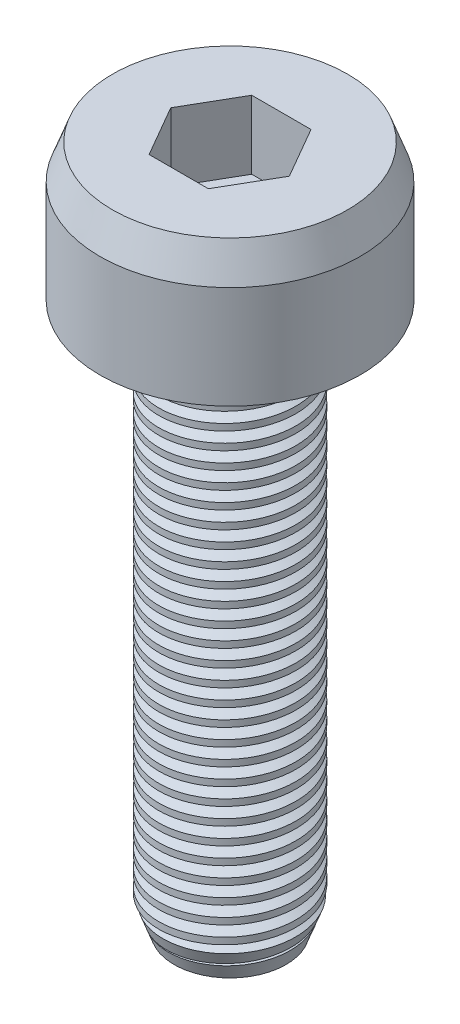
SolidWorks part; units mm, degrees
ref_plane "Front Plane" through (0, 0, 0) normal (0, 0, 1) x (1, 0, 0)
ref_plane "Top Plane" through (0, 0, 0) normal (0, 1, 0) x (1, 0, 0)
ref_plane "Right Plane" through (0, 0, 0) normal (1, 0, 0) x (0, 0, -1)
sketch "Sketch3" plane through (0, 0, 0) normal (0, 1, 0) x (1, 0, 0)
  circle A0 centre (0, 0) radius 1.9
  dimension "D1" = 3.8
extrude "Boss-Extrude3" add sketch "Sketch3" along normal blind 1.5
sketch "Sketch4" plane through (0, 1.5, 0) normal (0, 1, 0) x (1, 0, 0)
  circle A0 centre (0, 0) radius 1.9
  circle A1 centre (0, 0) radius 1.9 construction
  dimension "D1" = 3.8
extrude "Boss-Extrude5" add sketch "Sketch4" along normal blind 0.5 draft 20
sketch "Sketch6" plane through (0, 2, 0) normal (0, 1, 0) x (1, 0, 0)
  line L1 (0.866, 0) -> (0.433, 0.75)
  line L2 (0.433, 0.75) -> (-0.433, 0.75)
  line L3 (-0.433, 0.75) -> (-0.866, 0)
  line L4 (-0.866, 0) -> (-0.433, -0.75)
  line L5 (-0.433, -0.75) -> (0.433, -0.75)
  line L6 (0.433, -0.75) -> (0.866, 0)
  circle A0 centre (0, 0) radius 0.75 construction
  circle A1 centre (0, 0) radius 1.718 construction
  dimension "D1" = 1.5
extrude "Cut-Extrude1" cut sketch "Sketch6" against normal blind 1
sketch "Sketch7" plane through (0, 0, 0) normal (0, -1, 0) x (1, 0, 0)
  circle A0 centre (0, 0) radius 1
  circle A1 centre (0, 0) radius 1.9 construction
  dimension "D1" = 2
extrude "Boss-Extrude8" add sketch "Sketch7" along normal blind 7.5 contours A0
sketch "Sketch11" plane through (0, -7.5, 0) normal (0, -1, 0) x (1, 0, 0)
  circle A0 centre (0, 0) radius 1
  circle A1 centre (0, 0) radius 1 construction
  dimension "D1" = 2
extrude "Boss-Extrude9" add sketch "Sketch11" along normal blind 0.5 draft 20
sketch "Sketch12" plane through (0, -8, 0) normal (0, -1, 0) x (1, 0, 0)
  circle A0 centre (0, 0) radius 1
  circle A1 centre (0, 0) radius 0.818 construction
  dimension "D1" = 2
curve "Helix/Spiral2" pitch 0.25 height 8 turns 32
sketch "Sketch13" plane through (0, 0, 0) normal (0, 0, 1) x (1, 0, 0)
  line L1 (0.8667, -7.9956) -> (1.0572, -8.1056)
  line L2 (1.0572, -8.1056) -> (1.0572, -7.8856)
  line L3 (1.0572, -7.8856) -> (0.8667, -7.9956)
  circle A0 centre (0.9937, -7.9956) radius 0.0635 construction
  spline S0 degree 3 poles (1, -8) (1, -7.9948) (0.9479, -7.9844) (0.7255, -7.9688) (0.3926, -7.9531) (0, -7.9375) (-0.3926, -7.9219) (-0.7255, -7.9063) (-0.9479, -7.8906) (-1.026, -7.875) (-0.9479, -7.8594) (-0.7255, -7.8438) (-0.3926, -7.8281) (0, -7.8125) (0.3926, -7.7969) (0.7255, -7.7813) (0.9479, -7.7656) (1.026, -7.75) (0.9479, -7.7344) (0.7255, -7.7188) (0.3926, -7.7031) (0, -7.6875) (-0.3926, -7.6719) (-0.7255, -7.6562) (-0.9479, -7.6406) (-1.026, -7.625) (-0.9479, -7.6094) (-0.7255, -7.5937) (-0.3926, -7.5781) (0, -7.5625) (0.3926, -7.5469) (0.7255, -7.5312) (0.9479, -7.5156) (1.026, -7.5) (0.9479, -7.4844) (0.7255, -7.4687) (0.3926, -7.4531) (0, -7.4375) (-0.3926, -7.4219) (-0.7255, -7.4062) (-0.9479, -7.3906) (-1.026, -7.375) (-0.9479, -7.3594) (-0.7255, -7.3438) (-0.3926, -7.3281) (0, -7.3125) (0.3926, -7.2969) (0.7255, -7.2812) (0.9479, -7.2656) (1.026, -7.25) (0.9479, -7.2344) (0.7255, -7.2188) (0.3926, -7.2031) (0, -7.1875) (-0.3926, -7.1719) (-0.7255, -7.1563) (-0.9479, -7.1406) (-1.026, -7.125) (-0.9479, -7.1094) (-0.7255, -7.0937) (-0.3926, -7.0781) (0, -7.0625) (0.3926, -7.0469) (0.7255, -7.0312) (0.9479, -7.0156) (1.026, -7) (0.9479, -6.9844) (0.7255, -6.9687) (0.3926, -6.9531) (0, -6.9375) (-0.3926, -6.9219) (-0.7255, -6.9062) (-0.9479, -6.8906) (-1.026, -6.875) (-0.9479, -6.8594) (-0.7255, -6.8437) (-0.3926, -6.8281) (0, -6.8125) (0.3926, -6.7969) (0.7255, -6.7812) (0.9479, -6.7656) (1.026, -6.75) (0.9479, -6.7344) (0.7255, -6.7187) (0.3926, -6.7031) (0, -6.6875) (-0.3926, -6.6719) (-0.7255, -6.6562) (-0.9479, -6.6406) (-1.026, -6.625) (-0.9479, -6.6094) (-0.7255, -6.5937) (-0.3926, -6.5781) (0, -6.5625) (0.3926, -6.5469) (0.7255, -6.5312) (0.9479, -6.5156) (1.026, -6.5) (0.9479, -6.4844) (0.7255, -6.4687) (0.3926, -6.4531) (0, -6.4375) (-0.3926, -6.4219) (-0.7255, -6.4063) (-0.9479, -6.3906) (-1.026, -6.375) (-0.9479, -6.3594) (-0.7255, -6.3437) (-0.3926, -6.3281) (0, -6.3125) (0.3926, -6.2969) (0.7255, -6.2812) (0.9479, -6.2656) (1.026, -6.25) (0.9479, -6.2344) (0.7255, -6.2187) (0.3926, -6.2031) (0, -6.1875) (-0.3926, -6.1719) (-0.7255, -6.1562) (-0.9479, -6.1406) (-1.026, -6.125) (-0.9479, -6.1094) (-0.7255, -6.0937) (-0.3926, -6.0781) (0, -6.0625) (0.3926, -6.0469) (0.7255, -6.0312) (0.9479, -6.0156) (1.026, -6) (0.9479, -5.9844) (0.7255, -5.9687) (0.3926, -5.9531) (0, -5.9375) (-0.3926, -5.9219) (-0.7255, -5.9062) (-0.9479, -5.8906) (-1.026, -5.875) (-0.9479, -5.8594) (-0.7255, -5.8437) (-0.3926, -5.8281) (0, -5.8125) (0.3926, -5.7969) (0.7255, -5.7812) (0.9479, -5.7656) (1.026, -5.75) (0.9479, -5.7344) (0.7255, -5.7187) (0.3926, -5.7031) (0, -5.6875) (-0.3926, -5.6719) (-0.7255, -5.6562) (-0.9479, -5.6406) (-1.026, -5.625) (-0.9479, -5.6094) (-0.7255, -5.5937) (-0.3926, -5.5781) (0, -5.5625) (0.3926, -5.5469) (0.7255, -5.5312) (0.9479, -5.5156) (1.026, -5.5) (0.9479, -5.4844) (0.7255, -5.4687) (0.3926, -5.4531) (0, -5.4375) (-0.3926, -5.4219) (-0.7255, -5.4062) (-0.9479, -5.3906) (-1.026, -5.375) (-0.9479, -5.3594) (-0.7255, -5.3437) (-0.3926, -5.3281) (0, -5.3125) (0.3926, -5.2969) (0.7255, -5.2812) (0.9479, -5.2656) (1.026, -5.25) (0.9479, -5.2344) (0.7255, -5.2187) (0.3926, -5.2031) (0, -5.1875) (-0.3926, -5.1719) (-0.7255, -5.1562) (-0.9479, -5.1406) (-1.026, -5.125) (-0.9479, -5.1094) (-0.7255, -5.0937) (-0.3926, -5.0781) (0, -5.0625) (0.3926, -5.0469) (0.7255, -5.0312) (0.9479, -5.0156) (1.026, -5) (0.9479, -4.9844) (0.7255, -4.9687) (0.3926, -4.9531) (0, -4.9375) (-0.3926, -4.9219) (-0.7255, -4.9062) (-0.9479, -4.8906) (-1.026, -4.875) (-0.9479, -4.8594) (-0.7255, -4.8437) (-0.3926, -4.8281) (0, -4.8125) (0.3926, -4.7969) (0.7255, -4.7812) (0.9479, -4.7656) (1.026, -4.75) (0.9479, -4.7344) (0.7255, -4.7187) (0.3926, -4.7031) (0, -4.6875) (-0.3926, -4.6719) (-0.7255, -4.6562) (-0.9479, -4.6406) (-1.026, -4.625) (-0.9479, -4.6094) (-0.7255, -4.5937) (-0.3926, -4.5781) (0, -4.5625) (0.3926, -4.5469) (0.7255, -4.5312) (0.9479, -4.5156) (1.026, -4.5) (0.9479, -4.4844) (0.7255, -4.4687) (0.3926, -4.4531) (0, -4.4375) (-0.3926, -4.4219) (-0.7255, -4.4062) (-0.9479, -4.3906) (-1.026, -4.375) (-0.9479, -4.3594) (-0.7255, -4.3437) (-0.3926, -4.3281) (0, -4.3125) (0.3926, -4.2969) (0.7255, -4.2812) (0.9479, -4.2656) (1.026, -4.25) (0.9479, -4.2344) (0.7255, -4.2187) (0.3926, -4.2031) (0, -4.1875) (-0.3926, -4.1719) (-0.7255, -4.1562) (-0.9479, -4.1406) (-1.026, -4.125) (-0.9479, -4.1094) (-0.7255, -4.0937) (-0.3926, -4.0781) (0, -4.0625) (0.3926, -4.0469) (0.7255, -4.0312) (0.9479, -4.0156) (1.026, -4) (0.9479, -3.9844) (0.7255, -3.9687) (0.3926, -3.9531) (0, -3.9375) (-0.3926, -3.9219) (-0.7255, -3.9062) (-0.9479, -3.8906) (-1.026, -3.875) (-0.9479, -3.8594) (-0.7255, -3.8437) (-0.3926, -3.8281) (0, -3.8125) (0.3926, -3.7969) (0.7255, -3.7812) (0.9479, -3.7656) (1.026, -3.75) (0.9479, -3.7344) (0.7255, -3.7187) (0.3926, -3.7031) (0, -3.6875) (-0.3926, -3.6719) (-0.7255, -3.6562) (-0.9479, -3.6406) (-1.026, -3.625) (-0.9479, -3.6094) (-0.7255, -3.5937) (-0.3926, -3.5781) (0, -3.5625) (0.3926, -3.5469) (0.7255, -3.5312) (0.9479, -3.5156) (1.026, -3.5) (0.9479, -3.4844) (0.7255, -3.4687) (0.3926, -3.4531) (0, -3.4375) (-0.3926, -3.4219) (-0.7255, -3.4062) (-0.9479, -3.3906) (-1.026, -3.375) (-0.9479, -3.3594) (-0.7255, -3.3437) (-0.3926, -3.3281) (0, -3.3125) (0.3926, -3.2969) (0.7255, -3.2812) (0.9479, -3.2656) (1.026, -3.25) (0.9479, -3.2344) (0.7255, -3.2187) (0.3926, -3.2031) (0, -3.1875) (-0.3926, -3.1719) (-0.7255, -3.1562) (-0.9479, -3.1406) (-1.026, -3.125) (-0.9479, -3.1094) (-0.7255, -3.0937) (-0.3926, -3.0781) (0, -3.0625) (0.3926, -3.0469) (0.7255, -3.0312) (0.9479, -3.0156) (1.026, -3) (0.9479, -2.9844) (0.7255, -2.9687) (0.3926, -2.9531) (0, -2.9375) (-0.3926, -2.9219) (-0.7255, -2.9062) (-0.9479, -2.8906) (-1.026, -2.875) (-0.9479, -2.8594) (-0.7255, -2.8437) (-0.3926, -2.8281) (0, -2.8125) (0.3926, -2.7969) (0.7255, -2.7812) (0.9479, -2.7656) (1.026, -2.75) (0.9479, -2.7344) (0.7255, -2.7187) (0.3926, -2.7031) (0, -2.6875) (-0.3926, -2.6719) (-0.7255, -2.6562) (-0.9479, -2.6406) (-1.026, -2.625) (-0.9479, -2.6094) (-0.7255, -2.5937) (-0.3926, -2.5781) (0, -2.5625) (0.3926, -2.5469) (0.7255, -2.5312) (0.9479, -2.5156) (1.026, -2.5) (0.9479, -2.4844) (0.7255, -2.4687) (0.3926, -2.4531) (0, -2.4375) (-0.3926, -2.4219) (-0.7255, -2.4062) (-0.9479, -2.3906) (-1.026, -2.375) (-0.9479, -2.3594) (-0.7255, -2.3437) (-0.3926, -2.3281) (0, -2.3125) (0.3926, -2.2969) (0.7255, -2.2812) (0.9479, -2.2656) (1.026, -2.25) (0.9479, -2.2344) (0.7255, -2.2187) (0.3926, -2.2031) (0, -2.1875) (-0.3926, -2.1719) (-0.7255, -2.1562) (-0.9479, -2.1406) (-1.026, -2.125) (-0.9479, -2.1094) (-0.7255, -2.0937) (-0.3926, -2.0781) (0, -2.0625) (0.3926, -2.0469) (0.7255, -2.0312) (0.9479, -2.0156) (1.026, -2) (0.9479, -1.9844) (0.7255, -1.9687) (0.3926, -1.9531) (0, -1.9375) (-0.3926, -1.9219) (-0.7255, -1.9062) (-0.9479, -1.8906) (-1.026, -1.875) (-0.9479, -1.8594) (-0.7255, -1.8437) (-0.3926, -1.8281) (0, -1.8125) (0.3926, -1.7969) (0.7255, -1.7812) (0.9479, -1.7656) (1.026, -1.75) (0.9479, -1.7344) (0.7255, -1.7187) (0.3926, -1.7031) (0, -1.6875) (-0.3926, -1.6719) (-0.7255, -1.6562) (-0.9479, -1.6406) (-1.026, -1.625) (-0.9479, -1.6094) (-0.7255, -1.5937) (-0.3926, -1.5781) (0, -1.5625) (0.3926, -1.5469) (0.7255, -1.5312) (0.9479, -1.5156) (1.026, -1.5) (0.9479, -1.4844) (0.7255, -1.4687) (0.3926, -1.4531) (0, -1.4375) (-0.3926, -1.4219) (-0.7255, -1.4062) (-0.9479, -1.3906) (-1.026, -1.375) (-0.9479, -1.3594) (-0.7255, -1.3437) (-0.3926, -1.3281) (0, -1.3125) (0.3926, -1.2969) (0.7255, -1.2812) (0.9479, -1.2656) (1.026, -1.25) (0.9479, -1.2344) (0.7255, -1.2187) (0.3926, -1.2031) (0, -1.1875) (-0.3926, -1.1719) (-0.7255, -1.1562) (-0.9479, -1.1406) (-1.026, -1.125) (-0.9479, -1.1094) (-0.7255, -1.0937) (-0.3926, -1.0781) (0, -1.0625) (0.3926, -1.0469) (0.7255, -1.0312) (0.9479, -1.0156) (1.026, -1) (0.9479, -0.9844) (0.7255, -0.9687) (0.3926, -0.9531) (0, -0.9375) (-0.3926, -0.9219) (-0.7255, -0.9062) (-0.9479, -0.8906) (-1.026, -0.875) (-0.9479, -0.8594) (-0.7255, -0.8437) (-0.3926, -0.8281) (0, -0.8125) (0.3926, -0.7969) (0.7255, -0.7812) (0.9479, -0.7656) (1.026, -0.75) (0.9479, -0.7344) (0.7255, -0.7187) (0.3926, -0.7031) (0, -0.6875) (-0.3926, -0.6719) (-0.7255, -0.6562) (-0.9479, -0.6406) (-1.026, -0.625) (-0.9479, -0.6094) (-0.7255, -0.5937) (-0.3926, -0.5781) (0, -0.5625) (0.3926, -0.5469) (0.7255, -0.5312) (0.9479, -0.5156) (1.026, -0.5) (0.9479, -0.4844) (0.7255, -0.4687) (0.3926, -0.4531) (0, -0.4375) (-0.3926, -0.4219) (-0.7255, -0.4062) (-0.9479, -0.3906) (-1.026, -0.375) (-0.9479, -0.3594) (-0.7255, -0.3437) (-0.3926, -0.3281) (0, -0.3125) (0.3926, -0.2969) (0.7255, -0.2812) (0.9479, -0.2656) (1.026, -0.25) (0.9479, -0.2344) (0.7255, -0.2187) (0.3926, -0.2031) (0, -0.1875) (-0.3926, -0.1719) (-0.7255, -0.1562) (-0.9479, -0.1406) (-1.026, -0.125) (-0.9479, -0.1094) (-0.7255, -0.0937) (-0.3926, -0.0781) (0, -0.0625) (0.3926, -0.0469) (0.7255, -0.0312) (0.9479, -0.0156) (1, -0.0052) (1, 0) knots 0 0 0 0 0.001953 0.003906 0.005859 0.007812 0.009766 0.011719 0.013672 0.015625 0.017578 0.019531 0.021484 0.023437 0.025391 0.027344 0.029297 0.03125 0.033203 0.035156 0.037109 0.039062 0.041016 0.042969 0.044922 0.046875 0.048828 0.050781 0.052734 0.054687 0.056641 0.058594 0.060547 0.0625 0.064453 0.066406 0.068359 0.070312 0.072266 0.074219 0.076172 0.078125 0.080078 0.082031 0.083984 0.085937 0.087891 0.089844 0.091797 0.09375 0.095703 0.097656 0.099609 0.101562 0.103516 0.105469 0.107422 0.109375 0.111328 0.113281 0.115234 0.117187 0.119141 0.121094 0.123047 0.125 0.126953 0.128906 0.130859 0.132812 0.134766 0.136719 0.138672 0.140625 0.142578 0.144531 0.146484 0.148437 0.150391 0.152344 0.154297 0.15625 0.158203 0.160156 0.162109 0.164062 0.166016 0.167969 0.169922 0.171875 0.173828 0.175781 0.177734 0.179687 0.181641 0.183594 0.185547 0.1875 0.189453 0.191406 0.193359 0.195312 0.197266 0.199219 0.201172 0.203125 0.205078 0.207031 0.208984 0.210937 0.212891 0.214844 0.216797 0.21875 0.220703 0.222656 0.224609 0.226562 0.228516 0.230469 0.232422 0.234375 0.236328 0.238281 0.240234 0.242187 0.244141 0.246094 0.248047 0.25 0.251953 0.253906 0.255859 0.257812 0.259766 0.261719 0.263672 0.265625 0.267578 0.269531 0.271484 0.273437 0.275391 0.277344 0.279297 0.28125 0.283203 0.285156 0.287109 0.289062 0.291016 0.292969 0.294922 0.296875 0.298828 0.300781 0.302734 0.304687 0.306641 0.308594 0.310547 0.3125 0.314453 0.316406 0.318359 0.320312 0.322266 0.324219 0.326172 0.328125 0.330078 0.332031 0.333984 0.335937 0.337891 0.339844 0.341797 0.34375 0.345703 0.347656 0.349609 0.351562 0.353516 0.355469 0.357422 0.359375 0.361328 0.363281 0.365234 0.367187 0.369141 0.371094 0.373047 0.375 0.376953 0.378906 0.380859 0.382812 0.384766 0.386719 0.388672 0.390625 0.392578 0.394531 0.396484 0.398437 0.400391 0.402344 0.404297 0.40625 0.408203 0.410156 0.412109 0.414062 0.416016 0.417969 0.419922 0.421875 0.423828 0.425781 0.427734 0.429687 0.431641 0.433594 0.435547 0.4375 0.439453 0.441406 0.443359 0.445312 0.447266 0.449219 0.451172 0.453125 0.455078 0.457031 0.458984 0.460937 0.462891 0.464844 0.466797 0.46875 0.470703 0.472656 0.474609 0.476562 0.478516 0.480469 0.482422 0.484375 0.486328 0.488281 0.490234 0.492187 0.494141 0.496094 0.498047 0.5 0.501953 0.503906 0.505859 0.507812 0.509766 0.511719 0.513672 0.515625 0.517578 0.519531 0.521484 0.523437 0.525391 0.527344 0.529297 0.53125 0.533203 0.535156 0.537109 0.539062 0.541016 0.542969 0.544922 0.546875 0.548828 0.550781 0.552734 0.554687 0.556641 0.558594 0.560547 0.5625 0.564453 0.566406 0.568359 0.570312 0.572266 0.574219 0.576172 0.578125 0.580078 0.582031 0.583984 0.585937 0.587891 0.589844 0.591797 0.59375 0.595703 0.597656 0.599609 0.601562 0.603516 0.605469 0.607422 0.609375 0.611328 0.613281 0.615234 0.617187 0.619141 0.621094 0.623047 0.625 0.626953 0.628906 0.630859 0.632812 0.634766 0.636719 0.638672 0.640625 0.642578 0.644531 0.646484 0.648437 0.650391 0.652344 0.654297 0.65625 0.658203 0.660156 0.662109 0.664062 0.666016 0.667969 0.669922 0.671875 0.673828 0.675781 0.677734 0.679687 0.681641 0.683594 0.685547 0.6875 0.689453 0.691406 0.693359 0.695312 0.697266 0.699219 0.701172 0.703125 0.705078 0.707031 0.708984 0.710937 0.712891 0.714844 0.716797 0.71875 0.720703 0.722656 0.724609 0.726562 0.728516 0.730469 0.732422 0.734375 0.736328 0.738281 0.740234 0.742187 0.744141 0.746094 0.748047 0.75 0.751953 0.753906 0.755859 0.757812 0.759766 0.761719 0.763672 0.765625 0.767578 0.769531 0.771484 0.773437 0.775391 0.777344 0.779297 0.78125 0.783203 0.785156 0.787109 0.789062 0.791016 0.792969 0.794922 0.796875 0.798828 0.800781 0.802734 0.804687 0.806641 0.808594 0.810547 0.8125 0.814453 0.816406 0.818359 0.820312 0.822266 0.824219 0.826172 0.828125 0.830078 0.832031 0.833984 0.835937 0.837891 0.839844 0.841797 0.84375 0.845703 0.847656 0.849609 0.851562 0.853516 0.855469 0.857422 0.859375 0.861328 0.863281 0.865234 0.867187 0.869141 0.871094 0.873047 0.875 0.876953 0.878906 0.880859 0.882812 0.884766 0.886719 0.888672 0.890625 0.892578 0.894531 0.896484 0.898438 0.900391 0.902344 0.904297 0.90625 0.908203 0.910156 0.912109 0.914062 0.916016 0.917969 0.919922 0.921875 0.923828 0.925781 0.927734 0.929688 0.931641 0.933594 0.935547 0.9375 0.939453 0.941406 0.943359 0.945312 0.947266 0.949219 0.951172 0.953125 0.955078 0.957031 0.958984 0.960938 0.962891 0.964844 0.966797 0.96875 0.970703 0.972656 0.974609 0.976562 0.978516 0.980469 0.982422 0.984375 0.986328 0.988281 0.990234 0.992188 0.994141 0.996094 0.998047 1 1 1 1 construction
  dimension "D1" = 0.22
  dimension "D2" = 0.8667
sweep "Cut-Sweep2" cut profiles "Sketch13" path "Helix/Spiral2"
